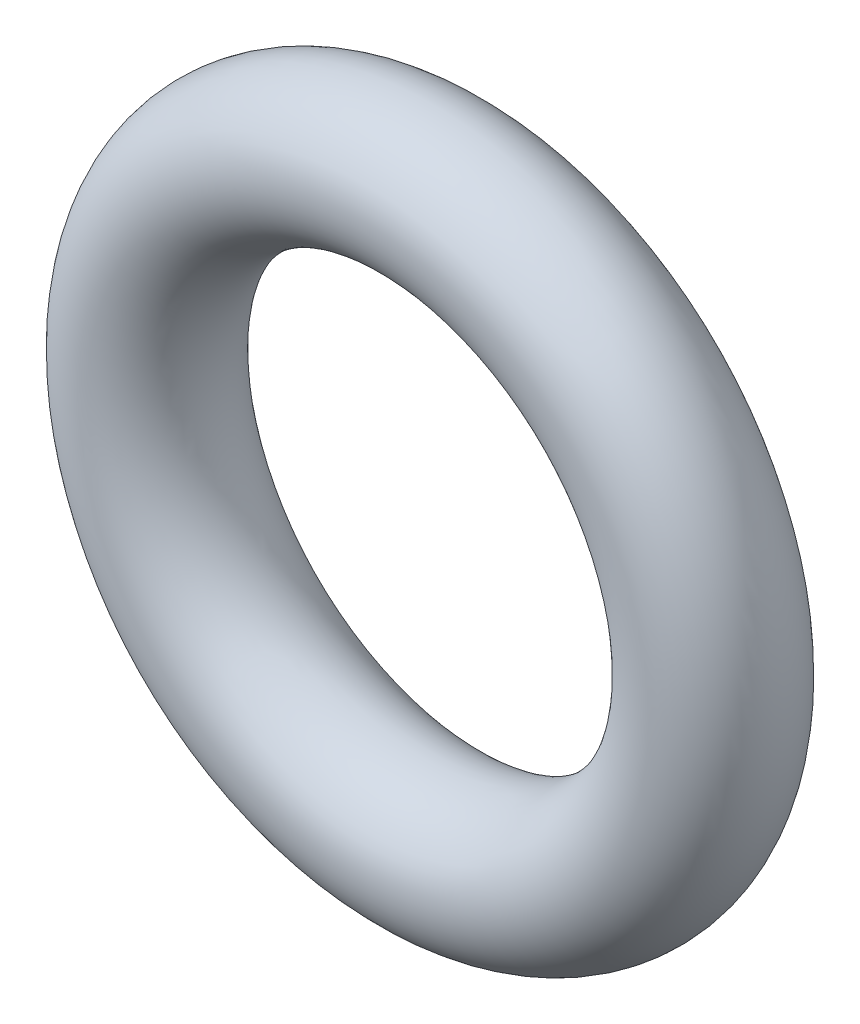
SolidWorks part; units mm, degrees
ref_plane "Front" through (0, 0, 0) normal (0, 0, 1) x (1, 0, 0)
ref_plane "Top" through (0, 0, 0) normal (0, 1, 0) x (1, 0, 0)
ref_plane "Right" through (0, 0, 0) normal (1, 0, 0) x (0, 0, -1)
sketch "Sketch1" plane through (0, 0, 0) normal (1, 0, 0) x (0, -1, 0)
  line L0 (0, -0.889) -> (0, 0.889) construction
  line L1 (-4.4196, 0.889) -> (4.4196, 0.889) construction
  line L2 (-1.5227, 0) -> (1.5227, 0) construction
  line L3 (-2.6416, 0) -> (2.6416, 0) construction
  circle A0 centre (3.5306, 0) radius 0.889
  point P9 (2.6416, 0)
  point P10 (4.4196, 0)
  point P13 (3.5306, 0.889)
  point P14 (3.5306, -0.889)
  point P16 (0, 0.889)
  dimension "Width" = 1.778
  dimension "ID" = 5.2832
  dimension "OD" = 8.8392
sketch "Sketch2" plane through (0, 0, 0) normal (1, 0, 0) x (0, 0, -1)
  circle A0 centre (0, -3.5306) radius 0.889 construction
  circle A1 centre (0, -3.5306) radius 0.889
revolve "Revolve1" add sketch "Sketch2" angle 360 about L0
ref_axis "Center Axis 1" through (0, 0, 0.889) along (0, 0, -1)
ref_plane "Contact Plane 1" through (0, 0, 0.889) normal (0, 0, 1) x (1, 0, 0)
ref_plane "Contact Plane 2" through (0, 0, -0.889) normal (0, 0, 1) x (1, 0, 0)
sketch "Sketch3" plane through (0, 0, 0) normal (0, 0, 1) x (1, 0, 0)
  circle A0 centre (0, 0) radius 1.9769
